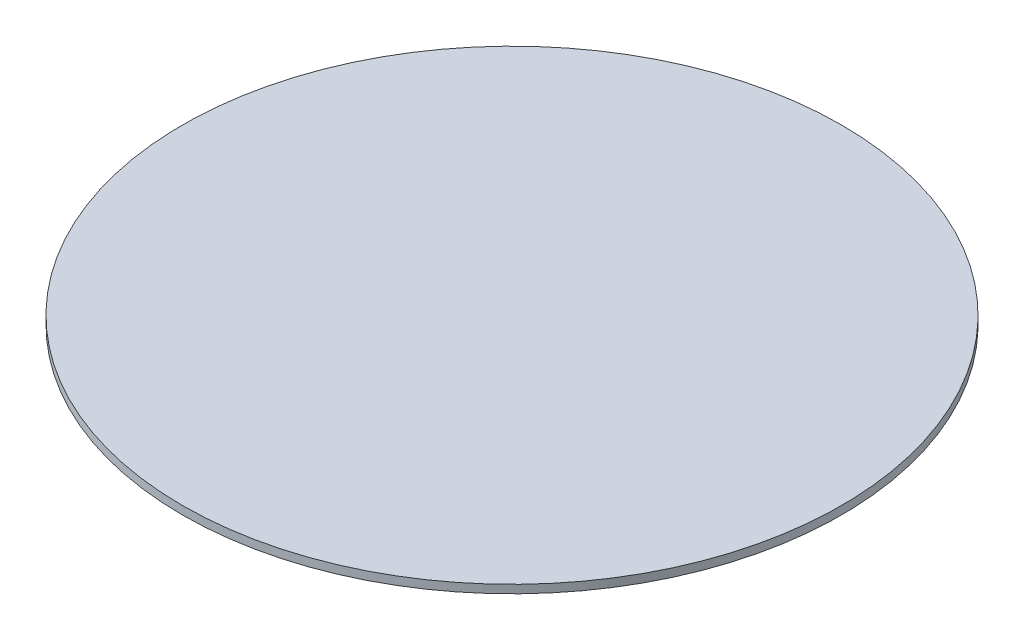
SolidWorks part; units mm, degrees
material "1060 Alloy"
ref_plane "Front Plane" through (0, 0, 0) normal (0, 0, 1) x (1, 0, 0)
ref_plane "Top Plane" through (0, 0, 0) normal (0, 1, 0) x (1, 0, 0)
ref_plane "Right Plane" through (0, 0, 0) normal (1, 0, 0) x (0, 0, -1)
sketch "Sketch1" plane through (0, 0, 0) normal (0, 1, 0) x (1, 0, 0)
  circle A0 centre (0, 0) radius 120
  dimension "D1" = 240
extrude "Boss-Extrude1" add sketch "Sketch1" along normal blind 3
